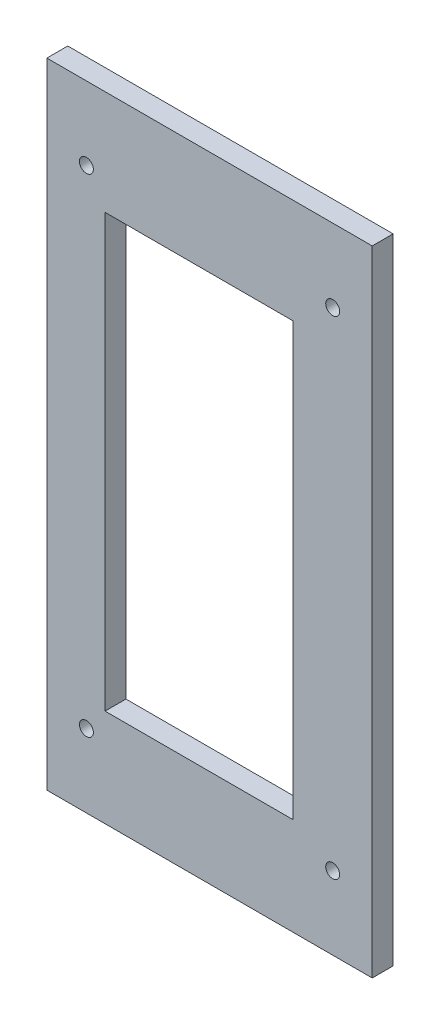
SolidWorks part; units mm, degrees
ref_plane "Front Plane" through (0, 0, 0) normal (0, 0, 1) x (1, 0, 0)
ref_plane "Top Plane" through (0, 0, 0) normal (0, 1, 0) x (1, 0, 0)
ref_plane "Right Plane" through (0, 0, 0) normal (1, 0, 0) x (0, 0, -1)
sketch "Sketch1" plane through (0, 0, 0) normal (0, 0, 1) x (1, 0, 0)
  line L0 (-17.675, 45.5) -> (-17.675, -45.5) construction
  line L1 (-23.35, 45.5) -> (23.35, 45.5)
  line L2 (-23.35, 45.5) -> (-23.35, -45.5)
  line L3 (-23.35, -45.5) -> (23.35, -45.5)
  line L4 (23.35, 45.5) -> (23.35, -45.5)
  line L5 (-23.35, 45.5) -> (23.35, -45.5) construction
  line L6 (-23.35, -45.5) -> (23.35, 45.5) construction
  line L7 (17.675, 45.5) -> (17.675, -45.5) construction
  line L8 (-15, 45.5) -> (-15, -45.5) construction
  line L9 (-15, 30.5) -> (12, 30.5)
  line L10 (-15, 30.5) -> (-15, -31.5)
  line L11 (-15, -31.5) -> (12, -31.5)
  line L12 (12, 30.5) -> (12, -31.5)
  line L13 (-20.35, -45.5) -> (-20.35, 45.5) construction
  line L14 (15, 45.5) -> (15, -45.5) construction
  line L15 (20.35, -45.5) -> (20.35, 45.5) construction
  line L16 (-21, 11.5) -> (21, 11.5) construction
  line L17 (-23.35, 0) -> (23.35, 0) construction
  line L18 (0, 45.5) -> (0, -45.5) construction
  circle A0 centre (17.675, 35) radius 1
  circle A1 centre (17.675, -35) radius 1
  circle A2 centre (-17.675, 35) radius 1
  circle A3 centre (-17.675, -35) radius 1
  point P0 (0, 0)
  dimension "D7" = 2
  dimension "D8" = 70
  dimension "D9" = 70
  dimension "D14" = 35
  dimension "D2" = 27
  dimension "D3" = 3
  dimension "D4" = 3
  dimension "D5" = 46.7
  dimension "D6" = 3
  dimension "D10" = 5.35
  dimension "D11" = 2.675
  dimension "D12" = 0
  dimension "5.65" = 5.35
  dimension "D13" = 2.675
  dimension "D15" = 19
  dimension "D16" = 43
  dimension "D17" = 15
  dimension "D18" = 10.5
  dimension "D20" = 91
extrude "Boss-Extrude1" add sketch "Sketch1" along normal blind 3
